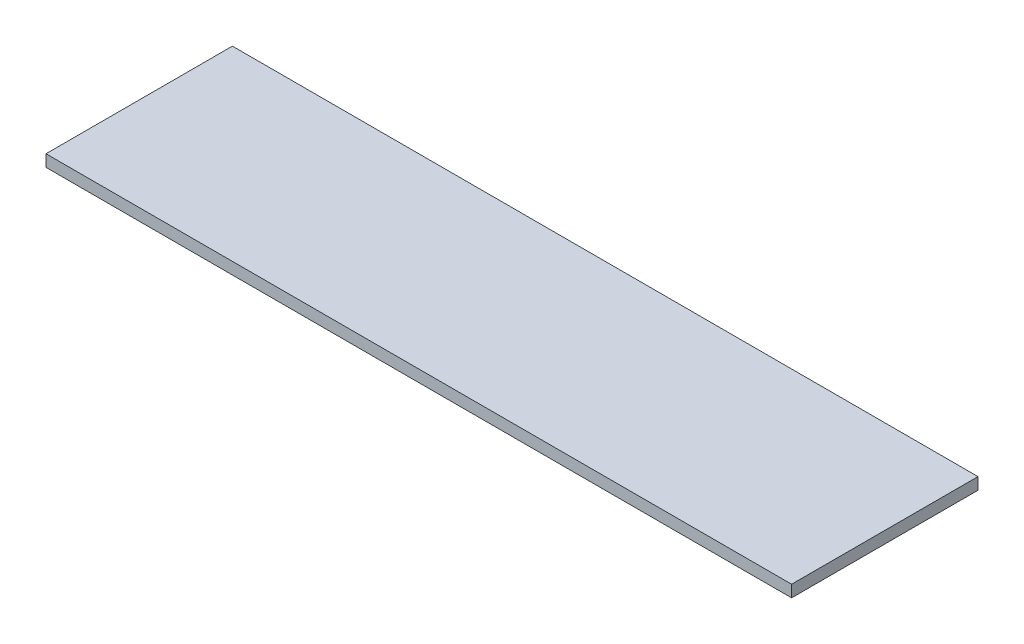
SolidWorks part; units mm, degrees
ref_plane "Front" through (0, 0, 0) normal (0, 0, 1) x (1, 0, 0)
ref_plane "Top" through (0, 0, 0) normal (0, 1, 0) x (1, 0, 0)
ref_plane "Right" through (0, 0, 0) normal (1, 0, 0) x (0, 0, -1)
sketch "Sketch1" plane through (0, 0, 0) normal (0, 1, 0) x (1, 0, 0)
  line L1 (0, 0) -> (200, 0)
  line L2 (0, 0) -> (0, -50)
  line L3 (0, -50) -> (200, -50)
  line L4 (200, 0) -> (200, -50)
  dimension "D1" = 200
  dimension "D2" = 50
extrude "Boss-Extrude1" add sketch "Sketch1" along normal blind 3.175
